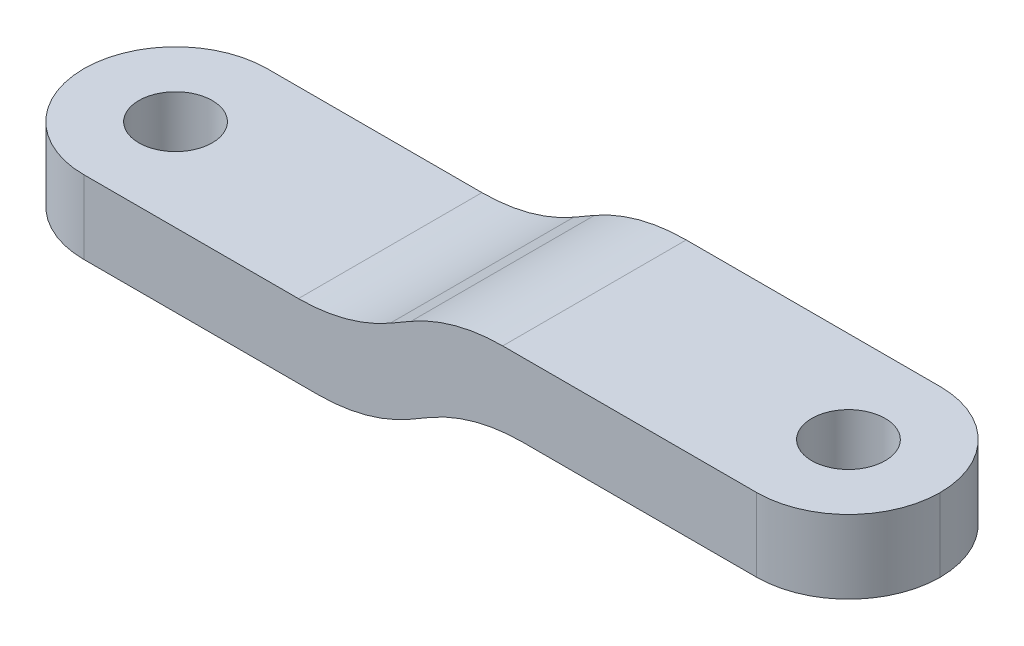
SolidWorks part; units mm, degrees
ref_plane "Alzado" through (0, 0, 0) normal (0, 0, 1) x (1, 0, 0)
ref_plane "Planta" through (0, 0, 0) normal (0, 1, 0) x (1, 0, 0)
ref_plane "Vista lateral" through (0, 0, 0) normal (1, 0, 0) x (0, 0, -1)
sketch "Croquis1" plane through (0, 0, 0) normal (0, 0, 1) x (1, 0, 0)
  line L0 (0, 0) -> (-30.6699, 0)
  line L1 (0, 0) -> (8.6603, 5)
  line L2 (8.6603, 5) -> (39.3301, 5)
  line L3 (7.0526, 11) -> (39.3301, 11)
  line L4 (-1.6077, 6) -> (7.0526, 11)
  line L5 (-1.6077, 6) -> (-30.6699, 6)
  line L6 (39.3301, 5) -> (39.3301, 11)
  line L7 (-30.6699, 0) -> (-30.6699, 6)
  dimension "D1" = 70
  dimension "D2" = 30
  dimension "D3" = 5
  dimension "D4" = 6
extrude "Saliente-Extruir1" add sketch "Croquis1" along normal mid plane 15
fillet "Redondeo1" radius 15 4 edges at (0, 0, 0) (8.6603, 5, 0) (-1.6077, 6, 0) (7.0526, 11, 0)
fillet "Redondeo2" radius 7.5 4 edges at (-30.6699, 3, -7.5) (-30.6699, 3, 7.5) (39.3301, 8, -7.5) (39.3301, 8, 7.5)
sketch "Croquis2" plane through (0, 6, 0) normal (0, 1, 0) x (1, 0, 0)
  circle A0 centre (-23.1699, 0) radius 3
  circle A1 centre (31.8301, 0) radius 3
  dimension "D1" = 6
extrude "Cortar-Extruir1" cut sketch "Croquis2" against normal through all both and the other way through all
